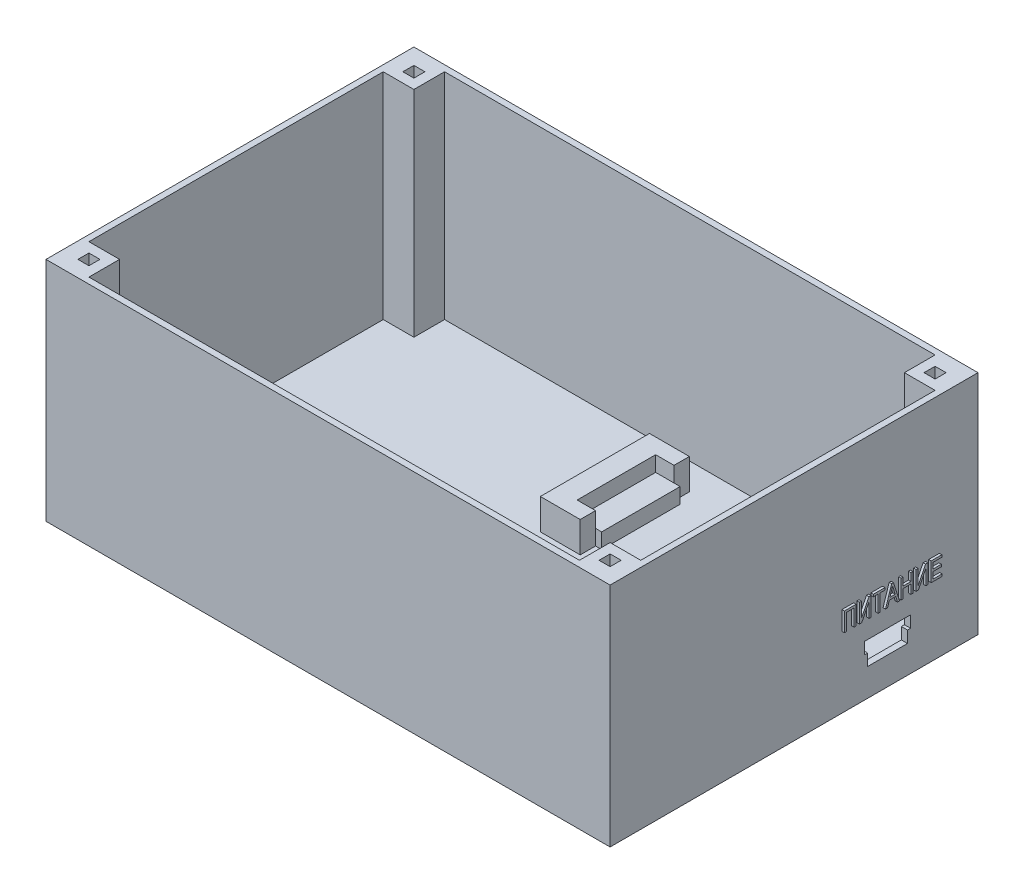
SolidWorks part; units mm, degrees
ref_plane "Спереди" through (0, 0, 0) normal (0, 0, 1) x (1, 0, 0)
ref_plane "Сверху" through (0, 0, 0) normal (0, 1, 0) x (1, 0, 0)
ref_plane "Справа" through (0, 0, 0) normal (1, 0, 0) x (0, 0, -1)
sketch "Эскиз2" plane through (0, 0, 0) normal (0, 1, 0) x (1, 0, 0)
  line L1 (0, 0) -> (92, 0)
  line L2 (0, 0) -> (0, 60)
  line L3 (0, 60) -> (92, 60)
  line L4 (92, 0) -> (92, 60)
extrude "Бобышка-Вытянуть1" add sketch "Эскиз2" along normal blind 2
sketch "Эскиз14" plane through (0, 2, 0) normal (0, 1, 0) x (1, 0, 0)
  line L0 (0, 60) -> (0, 0) construction
  line L1 (1, 59) -> (91, 59)
  line L2 (1, 59) -> (1, 1)
  line L3 (1, 1) -> (91, 1)
  line L4 (91, 59) -> (91, 1)
  line L5 (92, 60) -> (0, 60) construction
  line L6 (0, 0) -> (92, 0) construction
  line L7 (92, 0) -> (92, 60) construction
  line L9 (92, 0) -> (0, 0)
  line L10 (92, 0) -> (92, 60)
  line L11 (92, 60) -> (0, 60)
  line L12 (0, 0) -> (0, 60)
  dimension "D1" = 1
  dimension "D2" = 1
  dimension "D3" = 1
  dimension "D4" = 1
extrude "Бобышка-Вытянуть9" add sketch "Эскиз14" along normal blind 35 separate body
sketch "Эскиз16" plane through (0, 2, 0) normal (0, 1, 0) x (1, 0, 0)
  line L0 (1, 56.5) -> (6, 56.5) construction
  line L1 (6, 54) -> (1, 54)
  line L2 (6, 54) -> (6, 59)
  line L3 (6, 59) -> (1, 59)
  line L4 (1, 54) -> (1, 59)
  line L5 (3.5, 54) -> (3.5, 59) construction
  line L6 (86, 3.5) -> (91, 3.5) construction
  line L11 (91, 1) -> (86, 1)
  line L12 (91, 1) -> (91, 6)
  line L17 (91, 6) -> (86, 6)
  line L18 (86, 1) -> (86, 6)
  line L23 (88.5, 1) -> (88.5, 6) construction
  line L24 (1, 3.5) -> (6, 3.5) construction
  line L25 (6, 1) -> (1, 1)
  line L26 (6, 1) -> (6, 6)
  line L27 (6, 6) -> (1, 6)
  line L28 (1, 1) -> (1, 6)
  line L29 (3.5, 1) -> (3.5, 6) construction
  line L30 (86, 56.5) -> (91, 56.5) construction
  line L31 (91, 54) -> (86, 54)
  line L32 (91, 54) -> (91, 59)
  line L33 (91, 59) -> (86, 59)
  line L34 (86, 54) -> (86, 59)
  line L35 (88.5, 54) -> (88.5, 59) construction
  line L36 (88.5, 57.4) -> (88.5, 55.6) construction
  line L37 (87.6, 57.4) -> (89.4, 57.4)
  line L38 (87.6, 57.4) -> (87.6, 55.6)
  line L39 (87.6, 55.6) -> (89.4, 55.6)
  line L40 (89.4, 57.4) -> (89.4, 55.6)
  line L41 (87.6, 56.5) -> (89.4, 56.5) construction
  line L42 (3.5, 57.4) -> (3.5, 55.6) construction
  line L47 (2.6, 57.4) -> (4.4, 57.4)
  line L48 (2.6, 57.4) -> (2.6, 55.6)
  line L53 (2.6, 55.6) -> (4.4, 55.6)
  line L54 (4.4, 57.4) -> (4.4, 55.6)
  line L59 (2.6, 56.5) -> (4.4, 56.5) construction
  line L60 (3.5, 4.4) -> (3.5, 2.6) construction
  line L61 (2.6, 4.4) -> (4.4, 4.4)
  line L62 (2.6, 4.4) -> (2.6, 2.6)
  line L63 (2.6, 2.6) -> (4.4, 2.6)
  line L64 (4.4, 4.4) -> (4.4, 2.6)
  line L65 (2.6, 3.5) -> (4.4, 3.5) construction
  line L66 (88.5, 4.4) -> (88.5, 2.6) construction
  line L67 (87.6, 4.4) -> (89.4, 4.4)
  line L68 (87.6, 4.4) -> (87.6, 2.6)
  line L69 (87.6, 2.6) -> (89.4, 2.6)
  line L70 (89.4, 4.4) -> (89.4, 2.6)
  line L71 (87.6, 3.5) -> (89.4, 3.5) construction
  dimension "D2" = 5
  dimension "D3" = 5
  dimension "D5" = 5
  dimension "D6" = 5
  dimension "D8" = 5
  dimension "D9" = 5
  dimension "D11" = 5
  dimension "D12" = 5
sketch "Эскиз17" plane through (92, 0, 0) normal (1, 0, 0) x (0, 0, -1)
  line L0 (41.5, 8.3) -> (49, 8.3)
  line L1 (49, 8.3) -> (49, 6.4)
  line L2 (49, 6.4) -> (48.5, 6.4)
  line L3 (48.5, 6.4) -> (48.5, 4.5)
  line L4 (48.5, 4.5) -> (42, 4.5)
  line L5 (42, 4.5) -> (42, 6.4)
  line L6 (42, 6.4) -> (41.5, 6.4)
  line L7 (41.5, 6.4) -> (41.5, 8.3)
  line L8 (0, 2) -> (60, 2) construction
  line L9 (59, 37) -> (59, 2) construction
  dimension "D1" = 7.5
  dimension "D2" = 6.5
  dimension "D3" = 3.8
  dimension "D4" = 1.9
  dimension "D5" = 2.5
  dimension "D6" = 10
sketch "Эскиз18" plane through (0, 2, 0) normal (0, 1, 0) x (1, 0, 0)
  line L0 (91, 1) -> (91, 59) construction
  line L1 (47.3, 52.1241) -> (51.3, 52.1241)
  line L2 (47.3, 52.1241) -> (47.3, 39.3241)
  line L3 (47.3, 39.3241) -> (51.3, 39.3241)
  line L4 (51.3, 52.1241) -> (51.3, 39.3241)
  dimension "D1" = 12.8
  dimension "D2" = 4
  dimension "D3" = 43.7
extrude "Бобышка-Вытянуть12" add sketch "Эскиз18" along normal blind 2.5
sketch "Эскиз19" plane through (0, 2, 0) normal (0, 1, 0) x (1, 0, 0)
  line L1 (47.3, 39.3241) -> (50.3, 39.3241)
  line L2 (47.3, 39.3241) -> (47.3, 36.8241)
  line L3 (47.3, 36.8241) -> (50.3, 36.8241)
  line L4 (50.3, 39.3241) -> (50.3, 36.8241)
  line L5 (47.3, 52.1241) -> (50.3, 52.1241)
  line L6 (47.3, 52.1241) -> (47.3, 54.6241)
  line L7 (47.3, 54.6241) -> (50.3, 54.6241)
  line L8 (50.3, 52.1241) -> (50.3, 54.6241)
extrude "Бобышка-Вытянуть13" add sketch "Эскиз19" along normal blind 5
sketch "Эскиз20" plane through (0, 2, 0) normal (0, 1, 0) x (1, 0, 0)
  line L0 (47.3, 54.6241) -> (47.3, 36.8241) construction
  line L1 (47.3, 54.6241) -> (43.8, 54.6241)
  line L2 (47.3, 54.6241) -> (47.3, 36.8241)
  line L3 (47.3, 36.8241) -> (43.8, 36.8241)
  line L4 (43.8, 54.6241) -> (43.8, 36.8241)
extrude "Бобышка-Вытянуть14" add sketch "Эскиз20" along normal blind 5
extrude "Вырез-Вытянуть1" cut sketch "Эскиз17" against normal blind 5 contours L0 L1 L2 L3 L4 L5 L6 L7
sketch "Эскиз21" plane through (0, 2, 0) normal (0, 1, 0) x (1, 0, 0)
  line L0 (1, 6) -> (3.7061, 6)
  line L1 (88.2939, 6) -> (91, 6)
  line L2 (88.2939, 6) -> (88.2939, 26.3)
  line L3 (88.2939, 26.3) -> (91, 26.3)
  line L4 (91, 6) -> (91, 26.3)
  line L5 (1, 6) -> (1, 26.3)
  line L6 (1, 26.3) -> (3.7061, 26.3)
  line L7 (3.7061, 6) -> (3.7061, 26.3)
  line L9 (1, 59) -> (1, 1) construction
  line L11 (6, 6) -> (1, 6) construction
  point P8 (0, 0)
  point P9 (0, 0)
  point P14 (0, 0)
  dimension "D1" = 20.3
  dimension "D2" = 90
extrude "Бобышка-Вытянуть16" add sketch "Эскиз21" along normal blind 2.5
sketch "Эскиз22" plane through (0, 2, 0) normal (0, 1, 0) x (1, 0, 0)
  line L0 (1, 59) -> (1, 26.3) construction
  line L1 (3.7061, 26.3) -> (1, 26.3)
  line L2 (3.7061, 26.3) -> (3.7061, 28.8)
  line L3 (3.7061, 28.8) -> (1, 28.8)
  line L4 (1, 26.3) -> (1, 28.8)
  line L6 (91, 26.3) -> (88.2939, 26.3)
  line L7 (91, 26.3) -> (91, 28.8)
  line L8 (91, 28.8) -> (88.2939, 28.8)
  line L9 (88.2939, 26.3) -> (88.2939, 28.8)
extrude "Бобышка-Вытянуть17" add sketch "Эскиз22" along normal blind 5
extrude "Бобышка-Вытянуть19" add sketch "Эскиз16" along normal blind 35
sketch "Эскиз23" plane through (92, 0, 0) normal (1, 0, 0) x (0, 0, -1)
  text T0 "ПИТАНИЕ" font "Arial" height in points 12
extrude "Бобышка-Вытянуть20" add sketch "Эскиз23" along normal blind 0.4
